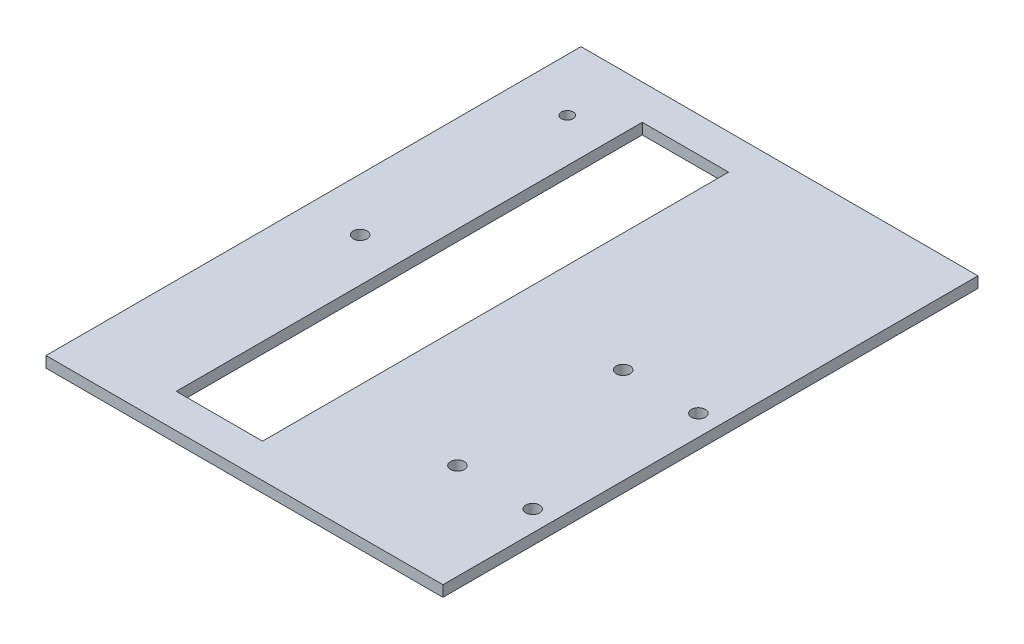
SolidWorks part; units mm, degrees
ref_plane "Front Plane" through (0, 0, 0) normal (0, 0, 1) x (1, 0, 0)
ref_plane "Top Plane" through (0, 0, 0) normal (0, 1, 0) x (1, 0, 0)
ref_plane "Right Plane" through (0, 0, 0) normal (1, 0, 0) x (0, 0, -1)
sketch "Sketch1" plane through (0, 0, 0) normal (0, 1, 0) x (1, 0, 0)
  line L0 (-19.4743, 15.0395) -> (5.5257, 15.0395) construction
  line L1 (67.6743, 92.6518) -> (67.6743, -62.3482)
  line L2 (67.6743, -62.3482) -> (-47.3257, -62.3482)
  line L3 (-47.3257, -62.3482) -> (-47.3257, -27.0446)
  line L4 (-6.9743, 75.2355) -> (-6.9743, -88.6335) construction
  line L5 (67.6743, 92.6518) -> (-47.3257, 92.6518)
  line L6 (-47.3257, -27.0446) -> (-47.3257, 92.6518)
  line L7 (-19.4743, 82.5395) -> (5.5257, 82.5395)
  line L8 (-19.4743, 82.5395) -> (-19.4743, -52.4605)
  line L9 (-19.4743, -52.4605) -> (5.5257, -52.4605)
  line L10 (5.5257, 82.5395) -> (5.5257, -52.4605)
  line L11 (50.7762, -62.3482) -> (50.7762, 92.6518) construction
  circle A0 centre (61.6743, 17.6518) radius 2
  circle A1 centre (61.6743, -30.3482) radius 2
  circle A2 centre (-32.0866, 13.4274) radius 2 construction
  circle A3 centre (-32.0866, 73.4274) radius 1.7 construction
  circle A4 centre (-32.0866, 13.4274) radius 2
  circle A5 centre (-32.0866, 73.4274) radius 1.7
  circle A6 centre (39.878, 17.6518) radius 2
  circle A7 centre (39.878, -30.3482) radius 2
  dimension "D2" = 4
  dimension "D3" = 4
  dimension "D1" = 25
  dimension "D4" = 48
  dimension "D5" = 6
  dimension "D6" = 115
  dimension "D7" = 135
  dimension "D8" = 32
  dimension "D9" = 155
extrude "Boss-Extrude1" add sketch "Sketch1" along normal blind 3.175
